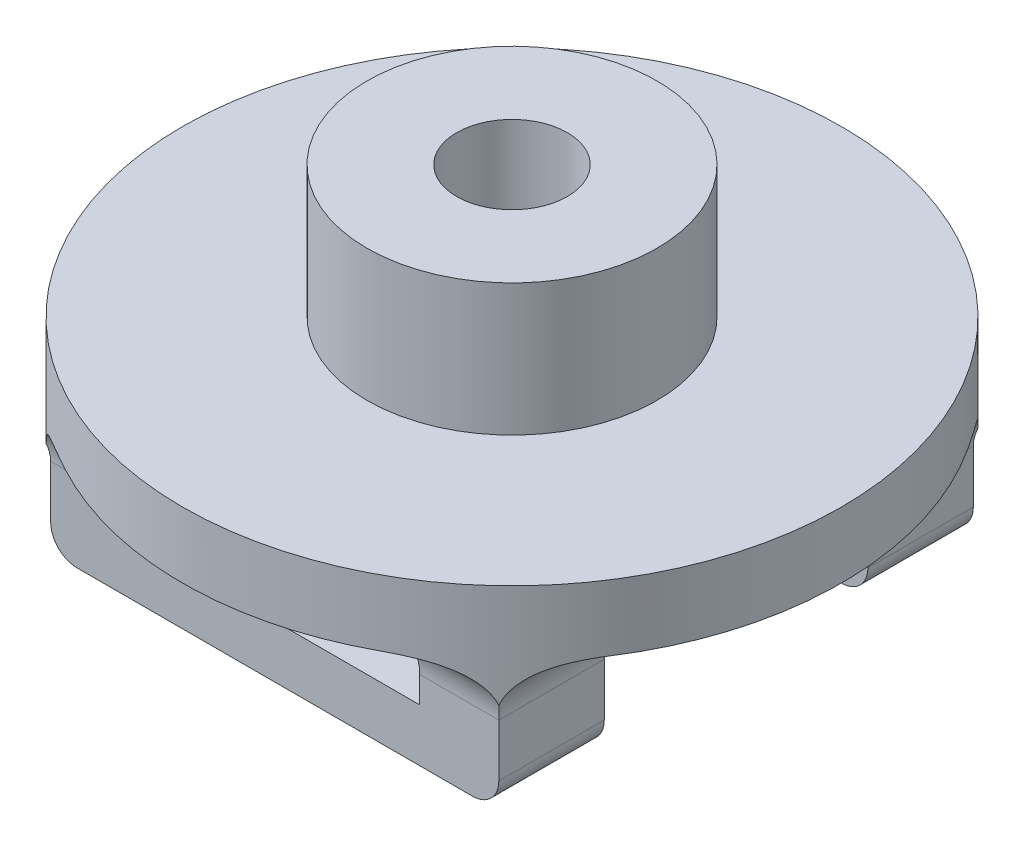
SolidWorks part; units mm, degrees
ref_plane "Front Plane" through (0, 0, 0) normal (0, 0, 1) x (1, 0, 0)
ref_plane "Top Plane" through (0, 0, 0) normal (0, 1, 0) x (1, 0, 0)
ref_plane "Right Plane" through (0, 0, 0) normal (1, 0, 0) x (0, 0, -1)
sketch "Sketch1" plane through (0, 0, 0) normal (0, 1, 0) x (1, 0, 0)
  circle A0 centre (0, 0) radius 12.5
  dimension "D1" = 25
extrude "Boss-Extrude1" add sketch "Sketch1" along normal blind 2.5
sketch "Sketch2" plane through (0, 2.5, 0) normal (0, 1, 0) x (1, 0, 0)
  circle A0 centre (0, 0) radius 5.5
  dimension "D1" = 11
extrude "Boss-Extrude2" add sketch "Sketch2" along normal blind 5
hole_wizard "Ø3.0mm Dowel Hole1" positions "Sketch3" profile "Sketch5" hole size "Ø3.0" standard "ANSI Metric"
sketch "Sketch3" plane through (0, 0, 0) normal (0, -1, 0) x (-1, 0, 0)
  point P0 (0, 0)
sketch "Sketch5" plane through (0, 0, 0) normal (1, 0, 0) x (0, 0, -1)
  line L0 (0, 0) -> (0, 11.2618)
  line L1 (0, 11.2618) -> (2.1, 10)
  line L2 (2.1, 10) -> (2.1, 0)
  line L5 (2.1, 0) -> (0, 0)
  line L10 (0, 11.2618) -> (-2.1, 10) construction
  line L11 (0, -6.35) -> (0, 107.95) construction
  dimension "Hole Dia." = 4.2
  dimension "Hole Depth" = 10
  dimension "Drill Angle" = 118
ref_plane "Plane1" through (0, 0, 8) normal (0, 0, 1) x (1, 0, 0)
sketch "Sketch6" plane through (0, 0, 8) normal (0, 0, 1) x (1, 0, 0)
  line L0 (-12.5, 0) -> (12.5, 0) construction
  line L1 (-8.5, 0) -> (8.5, 0)
  line L2 (-8.5, 0) -> (-8.5, -5)
  line L3 (-8.5, -5) -> (8.5, -5)
  line L4 (8.5, 0) -> (8.5, -5)
  line L5 (-12.5, 2.5) -> (-12.5, 0) construction
  line L6 (-5.5, 0) -> (5.5, 0)
  line L7 (-5.5, 0) -> (-5.5, -3)
  line L8 (-5.5, -3) -> (5.5, -3)
  line L9 (5.5, 0) -> (5.5, -3)
  line L10 (12.5, 0) -> (12.5, 2.5) construction
  dimension "D1" = 4
  dimension "D2" = 4
  dimension "D3" = 3
  dimension "D4" = 3
  dimension "D5" = 3
  dimension "D6" = 2
extrude "Boss-Extrude3" add sketch "Sketch6" against normal blind 3 and the other way blind 1 contours L1 L9 L8 L7 L2 L3 L4 region at (0, -3.1346, 8)
mirror "Mirror1" about plane through (0, 0, 0) normal (0, 0, 1) of "Boss-Extrude3"
fillet "Fillet1" radius 2 12 edges at (-7, 0, -9) (7, 0, -9) (-7, 0, 9) (7, 0, 9) (7, 0, 5) (-7, 0, 5) (-7, 0, -5) (7, 0, -5) (-8.5, 0, -7) (-8.5, 0, 7) (8.5, 0, 7) (8.5, 0, -7)
fillet "Fillet2" radius 1 4 edges at (-8.5, -5, 7) (8.5, -5, 7) (-8.5, -5, -7) (8.5, -5, -7)
